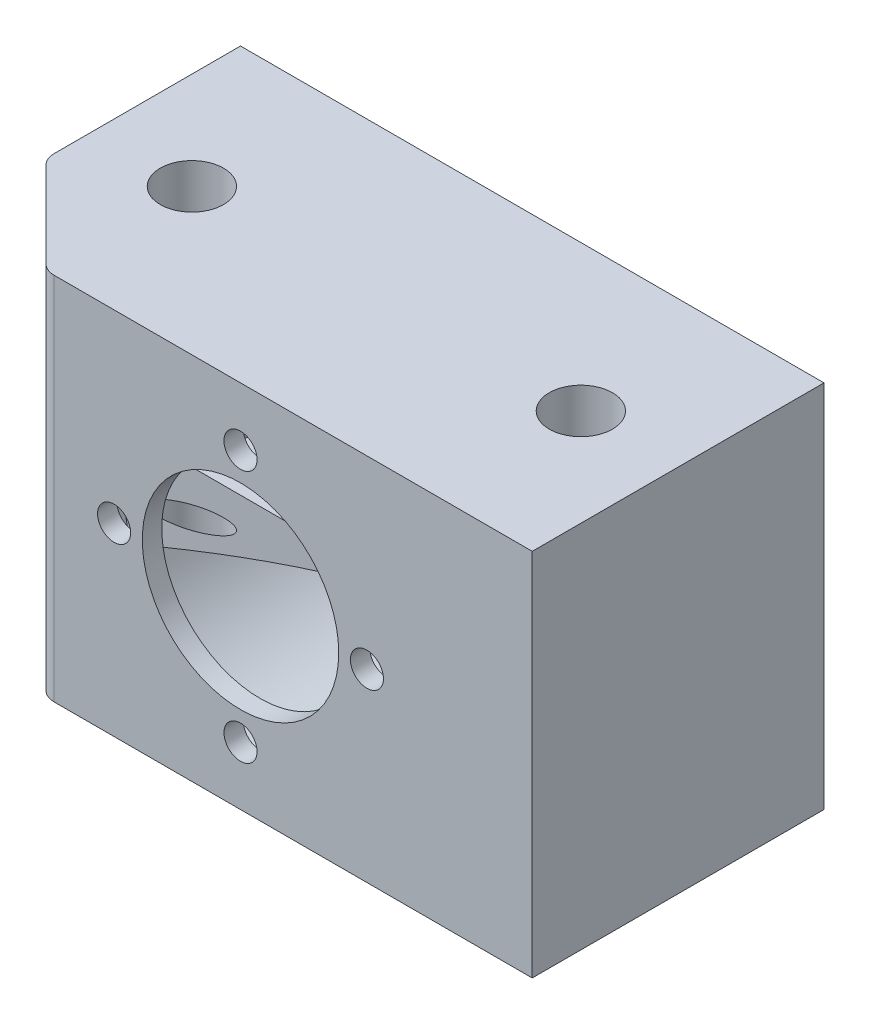
SolidWorks part; units mm, degrees
ref_plane "Plan de face" through (0, 0, 0) normal (0, 0, 1) x (1, 0, 0)
ref_plane "Plan de dessus" through (0, 0, 0) normal (0, 1, 0) x (1, 0, 0)
ref_plane "Plan de droite" through (0, 0, 0) normal (1, 0, 0) x (0, 0, -1)
sketch "Esquisse1" plane through (0, 0, 0) normal (1, 0, 0) x (0, 0, -1)
  line L0 (0, -19) -> (0, 19)
  line L1 (0, 19) -> (30, 19)
  line L2 (0, -19) -> (30, -19)
  line L3 (4, -15) -> (30, -15)
  line L4 (4, -15) -> (4, 15)
  line L5 (4, 15) -> (30, 15)
  line L6 (30, -19) -> (30, -15)
  line L7 (30, 15) -> (30, 19)
  point P4 (0, 0)
  dimension "D1" = 38
  dimension "D2" = 30
  dimension "D3" = 4
extrude "Boss.-Extru.1" add sketch "Esquisse1" along normal blind 60
chamfer "Chanfrein2" distance 10 distance2 20 1 edges at (30, 15, -4) first distance on face at (30, 0, -4)
chamfer "Chanfrein3" distance 20 distance2 10 1 edges at (30, -15, -4) first distance on face at (30, -15, -17)
fillet "Congé3" radius 2 2 edges at (30, 5, -4) (30, -5, -4)
sketch "Esquisse5" plane through (0, 0, 0) normal (0, 0, 1) x (1, 0, 0)
  line L0 (0, 0) -> (60, 0) construction
  line L1 (60, 19) -> (60, -19) construction
  circle A0 centre (30, 0) radius 16.05
  dimension "D1" = 32.1
extrude "Enlèv. mat.-Extru.4" cut sketch "Esquisse5" against normal through all and the other way blind 2 from offset 4 offset against normal yes
sketch "Esquisse2" plane through (0, 0, 0) normal (0, 0, 1) x (1, 0, 0)
  line L0 (30, 0) -> (30, 13) construction
  line L3 (0, 0) -> (60, 0) construction
  line L4 (0, 19) -> (0, -19) construction
  line L5 (60, 19) -> (60, -19) construction
  circle A0 centre (30, 13) radius 1.7
  circle A1 centre (43, 0) radius 1.7
  circle A2 centre (30, -13) radius 1.7
  circle A3 centre (17, 0) radius 1.7
  circle A4 centre (30, 0) radius 10.1
  point P0 (30, 0)
  point P19 (30, 0)
  dimension "D1" = 3.4
  dimension "D4" = 20.2
  dimension "D2" = 13
  dimension "D3" = 4
extrude "Enlèv. mat.-Extru.1" cut sketch "Esquisse2" against normal through all
sketch "Esquisse3" plane through (0, -19, 0) normal (0, -1, 0) x (1, 0, 0)
  line L0 (30, 0) -> (30, -30) construction
  line L1 (60, 0) -> (0, 0) construction
  line L2 (60, -30) -> (0, -30) construction
  line L3 (10, -15) -> (50, -15) construction
  circle A0 centre (10, -15) radius 1.6
  circle A1 centre (50, -15) radius 1.6
  point P9 (30, -15)
  dimension "D1" = 3.2
  dimension "D2" = 40
extrude "Enlèv. mat.-Extru.2" cut sketch "Esquisse3" against normal through all
sketch "Esquisse6" plane through (0, 0, 0) normal (0, 1, 0) x (1, 0, 0)
  circle A6 centre (50, 15) radius 1.6 construction
  circle A7 centre (10, 15) radius 1.6 construction
  circle A8 centre (50, 15) radius 1.6 construction
  circle A9 centre (10, 15) radius 1.6 construction
  circle A10 centre (10, 15) radius 3.25
  circle A11 centre (50, 15) radius 3.25
  dimension "D1" = 6.5
extrude "Enlèv. mat.-Extru.5" cut sketch "Esquisse6" against normal up to surface and the other way up to surface up to face at (10, -19, -16.6) other way up to face at (10, 19, -16.6)
chamfer "Chanfrein1" distance 10 angle 45 1 edges at (0, 0, 0)
sketch "Esquisse8" plane through (0, 19, 0) normal (0, 1, 0) x (1, 0, 0)
  line L1 (58.8, 30) -> (60, 30)
  line L2 (58.8, 30) -> (58.8, 0)
  line L3 (0, 30) -> (0, 10) construction
  line L4 (0, 10) -> (10, 0) construction
  line L5 (1.2, 30) -> (1.2, 10.4971)
  line L6 (1.2, 10.4971) -> (10.8485, 0.8485)
  line L7 (1.2, 30) -> (1.2, 10.4971)
  line L8 (1.2, 10.4971) -> (10.8485, 0.8485)
  line L9 (0, 30) -> (0, 10)
  line L10 (0, 10) -> (10, 0)
  line L11 (10, 0) -> (10.8485, 0.8485)
  line L12 (0, 30) -> (1.2, 30)
  line L13 (58.8, 30) -> (58.8, 0)
  line L14 (60, 30) -> (0, 30) construction
  line L15 (60, 30) -> (60, 0) construction
  line L16 (60, 30) -> (60, 0)
  line L17 (60, 0) -> (58.8, 0)
  dimension "D1" = 1.2
  dimension "D2" = 1.2
extrude "Boss.-Extru.3" add sketch "Esquisse8" against normal up to surface (38 mm away) up to face at (10, -19, -11.75)
fillet "Congé2" radius 2 2 edges at (10, 0, 0) (0, 0, -10)
